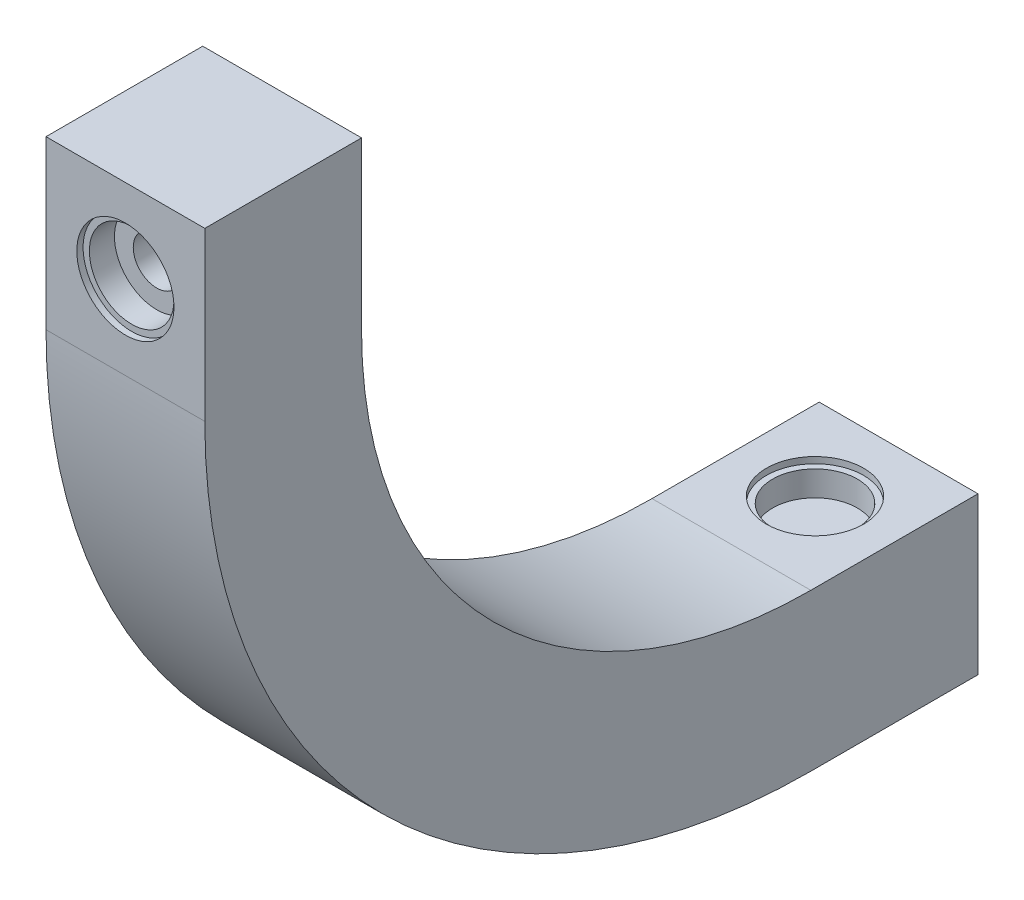
SolidWorks part; units mm, degrees
ref_plane "Front Plane" through (0, 0, 0) normal (0, 0, 1) x (1, 0, 0)
ref_plane "Top Plane" through (0, 0, 0) normal (0, 1, 0) x (1, 0, 0)
ref_plane "Right Plane" through (0, 0, 0) normal (1, 0, 0) x (0, 0, -1)
ref_axis "Z" through (0, 0, 109.5585) along (0, 0, -1)
ref_axis "X" through (8.36, 0, 0) along (-1, 0, 0)
sketch "Sketch4" plane through (0, 0, 0) normal (0, 0, 1) x (1, 0, 0)
  circle A0 centre (0, 0) radius 50 construction
  dimension "D1" = 100
sketch "Sketch5" plane through (0, 0, 0) normal (1, 0, 0) x (0, 0, -1)
  line L0 (-51, 8) -> (-51, 0)
  line L1 (-51, 0) -> (-51, -8)
  line L2 (-66, -8) -> (-66, 8)
  line L6 (-66, 8) -> (-51, 8)
  line L12 (-109.5585, 0) -> (-13.0351, 0) construction
  line L13 (0, 0) -> (-14.9091, -14.9091) construction
  line L14 (0, 0) -> (7.0065, 0) construction
  line L15 (0, -51) -> (-8, -51)
  line L16 (8, -51) -> (0, -51)
  line L17 (-8, -66) -> (8, -66)
  line L18 (8, -66) -> (8, -51)
  circle A0 centre (0, 0) radius 14 construction
  arc A1 (-51, -8) -> (-8, -51) centre (-8, -8) ccw
  arc A2 (-66, -8) -> (-8, -66) centre (-8, -8) ccw
  point P2 (9.4307, -21)
  point P4 (0, -2.1363)
  dimension "D1" = 28
  dimension "D4" = 8
  dimension "D2" = 45
  dimension "D3" = 15
  dimension "D5" = 51
sketch "Sketch6" plane through (0, 0, 0) normal (0, 1, 0) x (1, 0, 0)
  circle A0 centre (0, 0) radius 50 construction
  dimension "D1" = 100
extrude "Boss-Extrude1" add sketch "Sketch5" along normal blind 7.6 and the other way blind 7.6
sketch "Sketch7" plane through (0, 0, 0) normal (0, 0, 1) x (1, 0, 0)
  circle A0 centre (0, 0) radius 2.25
  dimension "D1" = 4.5
extrude "Cut-Extrude1" cut sketch "Sketch7" along normal through all
ref_axis "Y" through (0, -9.3489, 0) along (0, -1, 0)
sketch "Sketch16" plane through (0, 0, 0) normal (1, 0, 0) x (0, 0, -1)
  line L0 (0, -67) -> (0, 0) construction
  dimension "D1" = 67
ref_plane "Plane1" through (0, -67, 0) normal (0, 1, 0) x (1, 0, 0)
ref_axis "CX" through (0, -67, 4.4) along (0, 0, -1)
ref_plane "Plane2" through (0, 0, 0) normal (0, 0, -1) x (0, 1, 0)
ref_plane "Plane3" through (0, 0, 0) normal (1, 0, 0) x (0, 0, -1)
ref_axis "CZ" through (0, -8.7018, 0) along (0, -1, 0)
ref_axis "CY" through (-0.6471, -67, 0) along (1, 0, 0)
ref_point "CO"
sketch "Sketch15" plane through (0, -66, 0) normal (0, -1, 0) x (1, 0, 0)
  circle A0 centre (0, 0) radius 1.5
  dimension "D1" = 3
extrude "Cut-Extrude11" cut sketch "Sketch15" against normal blind 6
sketch "Sketch18" plane through (0, 0, 0) normal (1, 0, 0) x (0, 0, -1)
  line L0 (-66, 4.65) -> (-66, 0)
  line L1 (-66, 0) -> (-63, 0)
  line L2 (-63, 0) -> (-63, 4.05)
  line L3 (-63, 4.05) -> (-65.4, 4.05)
  line L4 (-65.4, 4.05) -> (-65.4, 4.65)
  line L5 (-65.4, 4.65) -> (-66, 4.65)
  line L6 (-68.6876, 0) -> (-58.5, 0) construction
  line L7 (-58.5, 0) -> (-58.5, 8) construction
  line L8 (-51.6, 4.65) -> (-51, 4.65)
  line L9 (-51.6, 4.05) -> (-51.6, 4.65)
  line L10 (-54, 4.05) -> (-51.6, 4.05)
  line L11 (-54, 0) -> (-54, 4.05)
  line L12 (-51, 0) -> (-54, 0)
  line L13 (-51, 4.65) -> (-51, 0)
  line L14 (-109.5585, 0) -> (-13.0351, 0) construction
  line L15 (-66, 8) -> (-51, 8) construction
  line L16 (-66, -8) -> (-66, 8) construction
  point P17 (0, 0)
  point P22 (-68.6876, 0)
  dimension "D1" = 0.6
  dimension "D2" = 8.1
  dimension "D3" = 3
  dimension "D4" = 4.65
revolve "Cut-Revolve1" cut sketch "Sketch18" angle 360 about axis through (0, 0, 109.5585) along (0, 0, -1)
pattern_circular "CirPattern1" count 2 over 90 about axis through (8.36, 0, 0) along (-1, 0, 0) of "Cut-Revolve1" reverse direction yes
equation "\"rbracket-width\"= \"L2Thickness\" + 0.2"
equation "\"EyeCaptureRadius\"= ( \"EyeDiameter\" + \"EyeClearance\" ) / 2"
equation "\"rbracket_planetocenterline_dist\"= \"BasePlaneDistance\""
equation "\"EyeDiameter\" = 100"
equation "\"BasePlaneDistance\" = \"EyeDiameter\"/2+\"L2Thickness\"+\"EyeClearance\""
equation "\"EyeClearance\" = 2"
equation "\"D1@Sketch4\"=\"EyeDiameter\""
equation "\"D1@Sketch6\"=\"EyeDiameter\""
equation "\"D1@Boss-Extrude1\"=\"rbracket-width\"/2"
equation "\"D2@Boss-Extrude1\"=\"rbracket-width\"/2"
equation "\"L2Thickness\" = 15"
equation "\"D3@Sketch5\"=\"L2Thickness\""
equation "\"D5@Sketch5\"=(\"EyeDiameter\"+\"EyeClearance\")/2"
equation "\"BearingThickness\"= 6"
equation "\"BearingOD\"=4.5"
equation "\"OuterBearingProudDistance\"= 0"
equation "\"FlangeOD\"=7.5"
equation "\"FlangeThickness\"= 0.75"
equation "\"PrinterFilamentThickness\"= 0.1'For setting distances for things like pressfits"
equation "\"ApplyPrinterOffset\"= 1'Set to 0 for line-to-line. Set to 1 for applying guestimate dimensions to make the printer produce good parts"
equation "\"D1@Cut-Extrude11\"=3*1.5"
equation "\"D1@Sketch16\"=\"BasePlaneDistance\""
equation "\"D2@Sketch18\"=\"ApplyPrinterOffset\"*\"PrinterFilamentThickness\" + 8"
equation "\"D4@Sketch18\"=4.6 + \"ApplyPrinterOffset\"*\"PrinterFilamentThickness\"/2"
